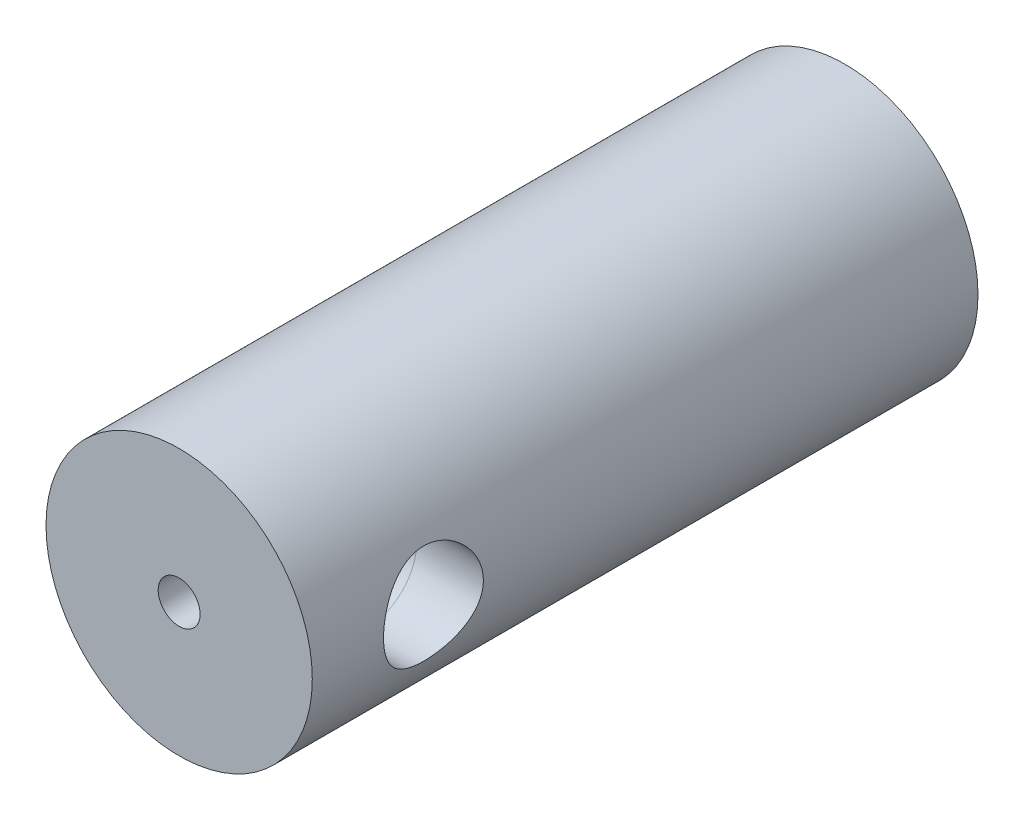
SolidWorks part; units mm, degrees
ref_plane "Front Plane" through (0, 0, 0) normal (0, 0, 1) x (1, 0, 0)
ref_plane "Top Plane" through (0, 0, 0) normal (0, 1, 0) x (1, 0, 0)
ref_plane "Right Plane" through (0, 0, 0) normal (1, 0, 0) x (0, 0, -1)
sketch "Sketch1" plane through (0, 0, 0) normal (0, 0, 1) x (1, 0, 0)
  circle A0 centre (0, 0) radius 20
  dimension "D1" = 40
extrude "Boss-Extrude1" add sketch "Sketch1" along normal blind 100
sketch "Sketch2" plane through (0, 0, 0) normal (0, 0, -1) x (-1, 0, 0)
  circle A0 centre (0, 0) radius 7.5
  dimension "D1" = 15
sketch "Sketch3" plane through (0, 0, 100) normal (0, 0, 1) x (1, 0, 0)
  circle A0 centre (0, 0) radius 3.15
  dimension "D1" = 6.3
extrude "Cut-Extrude2" cut sketch "Sketch3" against normal blind 5
sketch "Sketch4" plane through (0, 0, 0) normal (0, 1, 0) x (1, 0, 0)
  line L0 (0, 0) -> (0, -71.7939)
  line L1 (10, -81.7939) -> (20, -81.7939)
  line L3 (20, -100) -> (20, 0) construction
  arc A0 (0, -71.7939) -> (10, -81.7939) centre (10, -71.7939) ccw
  dimension "D1" = 10
sweep "Cut-Sweep1" cut profiles "Sketch2" path "Sketch4"
